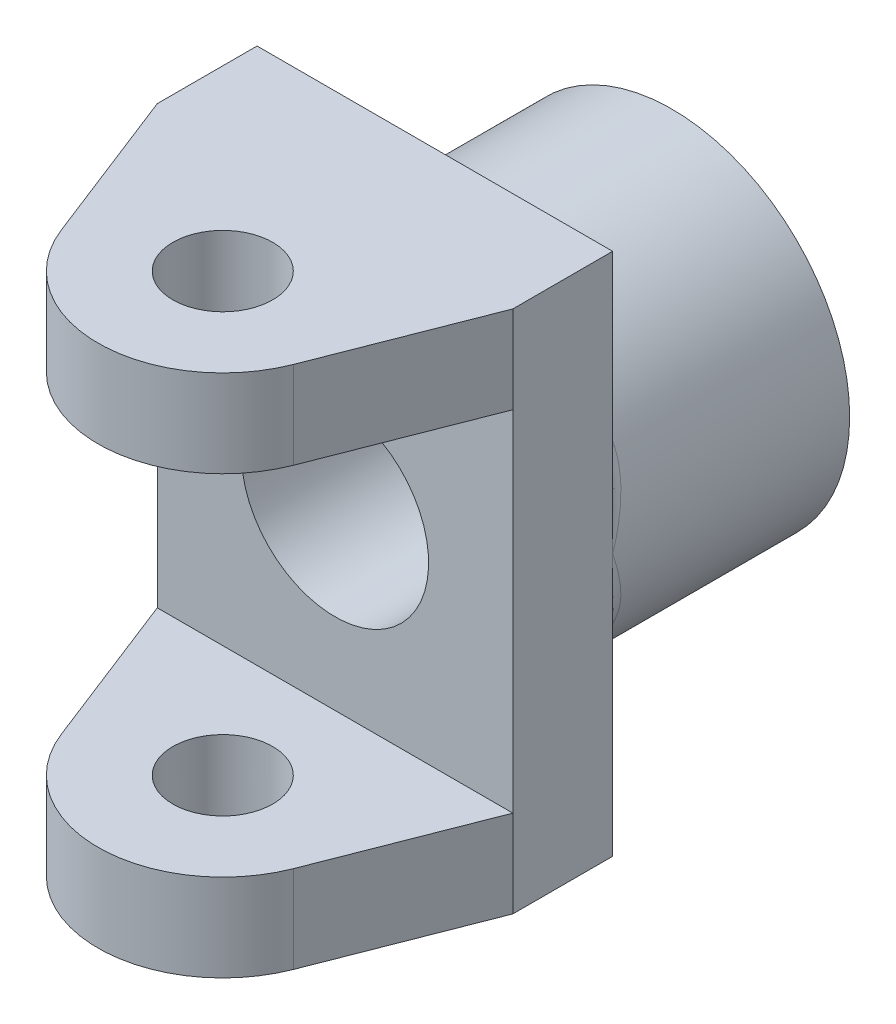
SolidWorks part; units mm, degrees
material "AISI 1020"
ref_plane "Front Plane" through (0, 0, 0) normal (0, 0, 1) x (1, 0, 0)
ref_plane "Top Plane" through (0, 0, 0) normal (0, 1, 0) x (1, 0, 0)
ref_plane "Right Plane" through (0, 0, 0) normal (1, 0, 0) x (0, 0, -1)
sketch "Sketch1" plane through (0, 0, 0) normal (0, 0, 1) x (1, 0, 0)
  circle A0 centre (0, 0) radius 28.5
  dimension "D1" = 57
extrude "Boss-Extrude1" add sketch "Sketch1" along normal blind 38
sketch "Sketch4" plane through (0, 0, 0) normal (1, 0, 0) x (0, 0, -1)
  line L0 (0, 28.5) -> (0, 42)
  line L1 (16, 42) -> (16, -42)
  line L2 (0, -28.5) -> (0, -42)
  line L3 (0, 42) -> (16, 42)
  line L4 (0, 28.5) -> (0, -28.5)
  line L5 (0, -42) -> (16, -42)
  dimension "D1" = 84
  dimension "D2" = 16
  dimension "D3" = 42
sketch "Sketch5" plane through (0, 0, 38) normal (0, 0, 1) x (1, 0, 0)
  line L0 (0, 42) -> (-28.5, 42)
  line L1 (0, 28.5) -> (0, -28.5) construction
  line L2 (0, 42) -> (0, -42) construction
  line L3 (-28.5, 42) -> (-28.5, 28)
  line L4 (-28.5, 28) -> (28.5, 28)
  line L5 (28.5, 28) -> (28.5, 42)
  line L6 (28.5, 42) -> (0, 42)
  circle A1 centre (0, 0) radius 28.5 construction
  point P6 (0, 28)
  dimension "D2" = 14
  dimension "D3" = 28
extrude "Boss-Extrude3" add sketch "Sketch5" along normal blind 16
mirror "Mirror1" about plane through (0, 0, 0) normal (0, 1, 0) of "Boss-Extrude3"
sketch "Sketch7" plane through (0, 42, 0) normal (0, 1, 0) x (1, 0, 0)
  line L0 (18.6299, -79.2751) -> (28.5, -54)
  line L1 (-18.6299, -79.2751) -> (-28.5, -54)
  line L2 (-28.5, -54) -> (28.5, -54)
  arc A0 (-18.6299, -79.2751) -> (18.6299, -79.2751) centre (0, -72) ccw
  dimension "D1" = 40
  dimension "D2" = 72
extrude "Boss-Extrude4" add sketch "Sketch7" against normal blind 14
mirror "Mirror2" about plane through (0, 0, 0) normal (0, 1, 0) of "Boss-Extrude3", "Boss-Extrude4"
sketch "Sketch8" plane through (0, 42, 0) normal (0, 1, 0) x (1, 0, 0)
  circle A0 centre (0, -72) radius 8
  dimension "D1" = 16
extrude "Cut-Extrude2" cut sketch "Sketch8" against normal blind 111
sketch "Sketch9" plane through (-28.5, 0, 0) normal (-1, 0, 0) x (0, 0, 1)
  line L0 (38, 42) -> (38, -42)
  line L1 (38, -42) -> (54, -42)
  line L2 (54, -42) -> (54, 42)
  line L3 (54, 42) -> (38, 42)
extrude "Boss-Extrude5" add sketch "Sketch9" against normal up to surface (57 mm away) up to face at (28.5, 35, 46)
fillet "Fillet1" radius 3 2 edges at (0, -28.5, 38) (0, 28.5, 38)
sketch "Sketch10" plane through (0, 0, 0) normal (0, 0, -1) x (-1, 0, 0)
  circle A0 centre (0, 0) radius 15
  dimension "D1" = 30
extrude "Cut-Extrude3" cut sketch "Sketch10" against normal through all both
sketch "Sketch12" plane through (0, 0, 0) normal (0, 0, 1) x (1, 0, 0)
  line L1 (4, 18.5) -> (-4, 18.5)
  line L2 (4, 18.5) -> (4, 11.5)
  line L3 (4, 11.5) -> (-4, 11.5)
  line L4 (-4, 18.5) -> (-4, 11.5)
  line L5 (4, 18.5) -> (-4, 11.5) construction
  line L6 (4, 11.5) -> (-4, 18.5) construction
  circle A0 centre (0, 0) radius 15 construction
  point P0 (0, 15)
  dimension "D1" = 8
  dimension "D2" = 7
extrude "Cut-Extrude5" cut sketch "Sketch12" along normal through all both
scale "Scale1" scale about centroid uniform scaling yes scale factor 2
